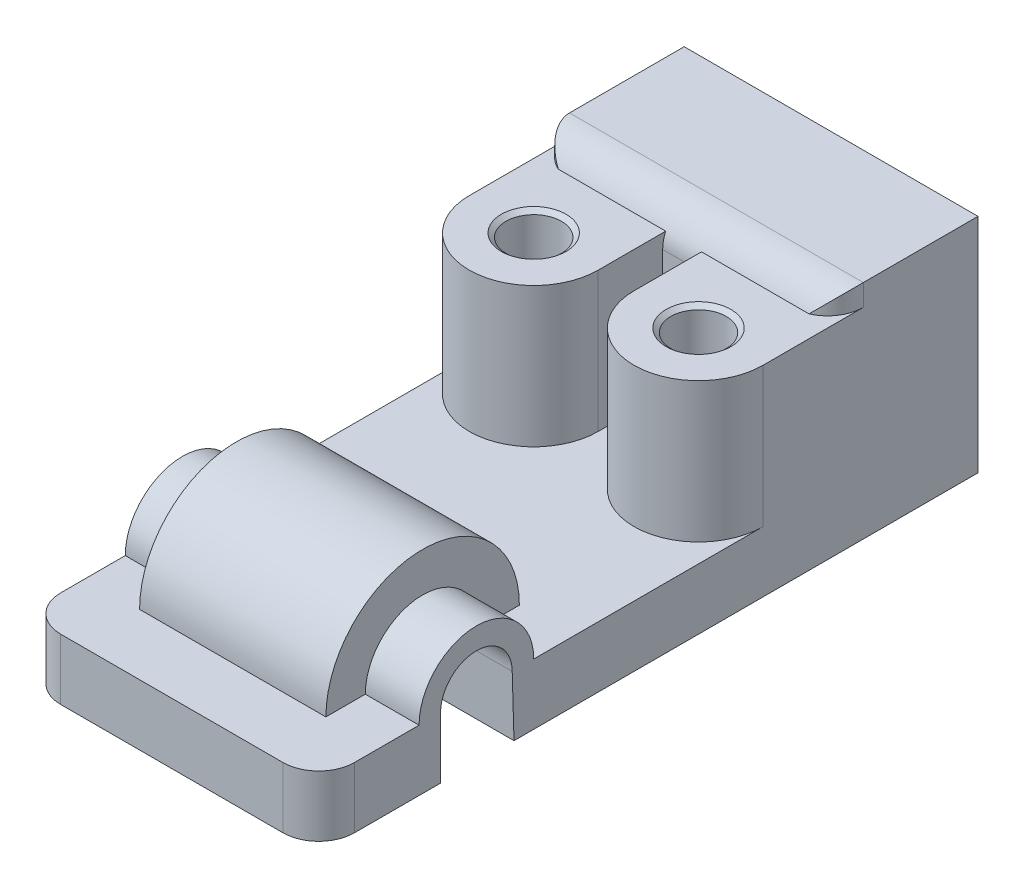
SolidWorks part; units mm, degrees
material "AISI 1020"
ref_plane "Front Plane" through (0, 0, 0) normal (0, 0, 1) x (1, 0, 0)
ref_plane "Top Plane" through (0, 0, 0) normal (0, 1, 0) x (1, 0, 0)
ref_plane "Right Plane" through (0, 0, 0) normal (1, 0, 0) x (0, 0, -1)
sketch "Sketch3" plane through (0, 0, 0) normal (1, 0, 0) x (0, 0, -1)
  line L0 (0, 0) -> (184, 0)
  line L1 (184, 0) -> (184, 62)
  line L2 (184, 62) -> (142, 62)
  line L3 (142, 62) -> (142, 17)
  line L4 (142, 17) -> (0, 17)
  line L5 (0, 17) -> (0, 0)
  dimension "D1" = 184
  dimension "D2" = 62
  dimension "D3" = 42
  dimension "D4" = 17
extrude "Boss-Extrude2" add sketch "Sketch3" along normal mid plane 82
sketch "Sketch4" plane through (0, 17, 0) normal (0, 1, 0) x (1, 0, 0)
  line L0 (41, 142) -> (41, 124)
  line L1 (41, 142) -> (41, 0) construction
  line L2 (5, 124) -> (5, 142)
  line L3 (41, 142) -> (-41, 142) construction
  line L4 (41, 184) -> (-41, 184) construction
  line L5 (5, 142) -> (41, 142)
  arc A0 (41, 124) -> (5, 124) centre (23, 124) cw
  dimension "D1" = 18
  dimension "D2" = 60
extrude "Boss-Extrude4" add sketch "Sketch4" along normal blind 39 contours A0 L2 L5 L0
hole_wizard "M18 Tapped Hole1" positions "Sketch5" profile "Sketch6" tap size "M18" standard "DIN"
sketch "Sketch5" plane through (0, 56, 0) normal (0, 1, 0) x (1, 0, 0)
  point P0 (23, 124)
sketch "Sketch6" plane through (23, 56, -124) normal (1, 0, 0) x (0, 0, 1)
  line L0 (0, 0) -> (0, 31.6567)
  line L1 (0, 31.6567) -> (7.75, 27)
  line L2 (7.75, 27) -> (7.75, 1.0699)
  line L3 (7.75, 1.0699) -> (9.025, 0)
  line L5 (9.025, 0) -> (0, 0)
  line L6 (-7.75, 1.0699) -> (-9.025, 0) construction
  line L10 (0, 31.6567) -> (-7.75, 27) construction
  line L11 (0, -6.35) -> (0, 107.95) construction
  dimension "Tap Drill Dia." = 15.5
  dimension "Tap Drill Depth" = 27
  dimension "Near C'Sink Dia." = 18.05
  dimension "Near C'Sink Angle" = 100
  dimension "Drill Angle" = 118
cosmetic thread "Hole Thread1" parameters "D1"=24, "D2"=18
mirror "Mirror1" about plane through (0, 0, 0) normal (1, 0, 0) of "M18 Tapped Hole1", "Boss-Extrude4"
cosmetic thread "Hole Thread2" parameters "D1"=24, "D2"=18
sketch "Sketch10" plane through (0, 0, 0) normal (1, 0, 0) x (0, 0, -1)
  line L0 (124, 17) -> (0, 17) construction
  line L1 (17, 17) -> (71, 17)
  arc A0 (71, 17) -> (17, 17) centre (44, 17) ccw
  arc A1 (60, 17) -> (28, 17) centre (44, 17) ccw
  arc A2 (54, 17) -> (34, 17) centre (44, 17) ccw
  dimension "D1" = 10
  dimension "D2" = 16
  dimension "D3" = 27
  dimension "D4" = 140
extrude "Boss-Extrude6" add sketch "Sketch10" along normal through all and the other way through all contours A2 L1 A1 region at (0, 32.6422, -44)
extrude "Boss-Extrude7" add sketch "Sketch10<3>" along normal mid plane 52 contours A1 L1 A0 region at (0, 43.3963, -44)
sketch "Sketch10<3>" plane through (0, 0, 0) normal (1, 0, 0) x (0, 0, -1) same geometry as "Sketch10"
sketch "Sketch11" plane through (41, 0, 0) normal (1, 0, 0) x (0, 0, -1)
  line L0 (34, 17) -> (34, 0)
  line L2 (0, 0) -> (184, 0) construction
  line L3 (34, 0) -> (54.4993, 0)
  line L4 (54.4993, 0) -> (54, 17)
  line L5 (54, 17) -> (34, 17) construction
  line L6 (54, 17) -> (34, 17)
  arc A0 (54, 17) -> (34, 17) centre (44, 17) ccw construction
  arc A1 (54, 17) -> (34, 17) centre (44, 16.7063) ccw
  line M5 (0, 0) -> (184, 0)
  line M12 (54, 17) -> (34, 17)
extrude "Cut-Extrude1" cut sketch "Sketch11" against normal through all contours L4 L0 M5 M12 | A1 M12 region at (41, 8.4651, -44.1253) region at (41, 21.1114, -44)
sketch "Sketch12" plane through (0, 0, 0) normal (0, -1, 0) x (1, 0, 0)
  line L0 (41, -184) -> (-41, -184) construction
  line L1 (-33, -184) -> (33, -184)
  line L2 (-33, -184) -> (-33, -148)
  line L3 (-33, -148) -> (33, -148)
  line L4 (33, -184) -> (33, -148)
  line L5 (0, 0) -> (0, -75.7654) construction
  dimension "D1" = 66
  dimension "D2" = 36
extrude "Cut-Extrude5" cut sketch "Sketch12" against normal blind 50 from offset 6 offset against normal yes
fillet "Fillet1" radius 10 5 edges at (0, 62, -142) (41, 59, -142) (-41, 59, -142) (-41, 8.5, 0) (41, 8.5, 0)
sketch "Sketch13" plane through (-41, 0, 0) normal (-1, 0, 0) x (0, 0, 1)
  circle A0 centre (-166, 47.1906) radius 10
  dimension "D1" = 20
  dimension "D2" = 18
extrude "Cut-Extrude6" cut sketch "Sketch13" against normal blind 50
